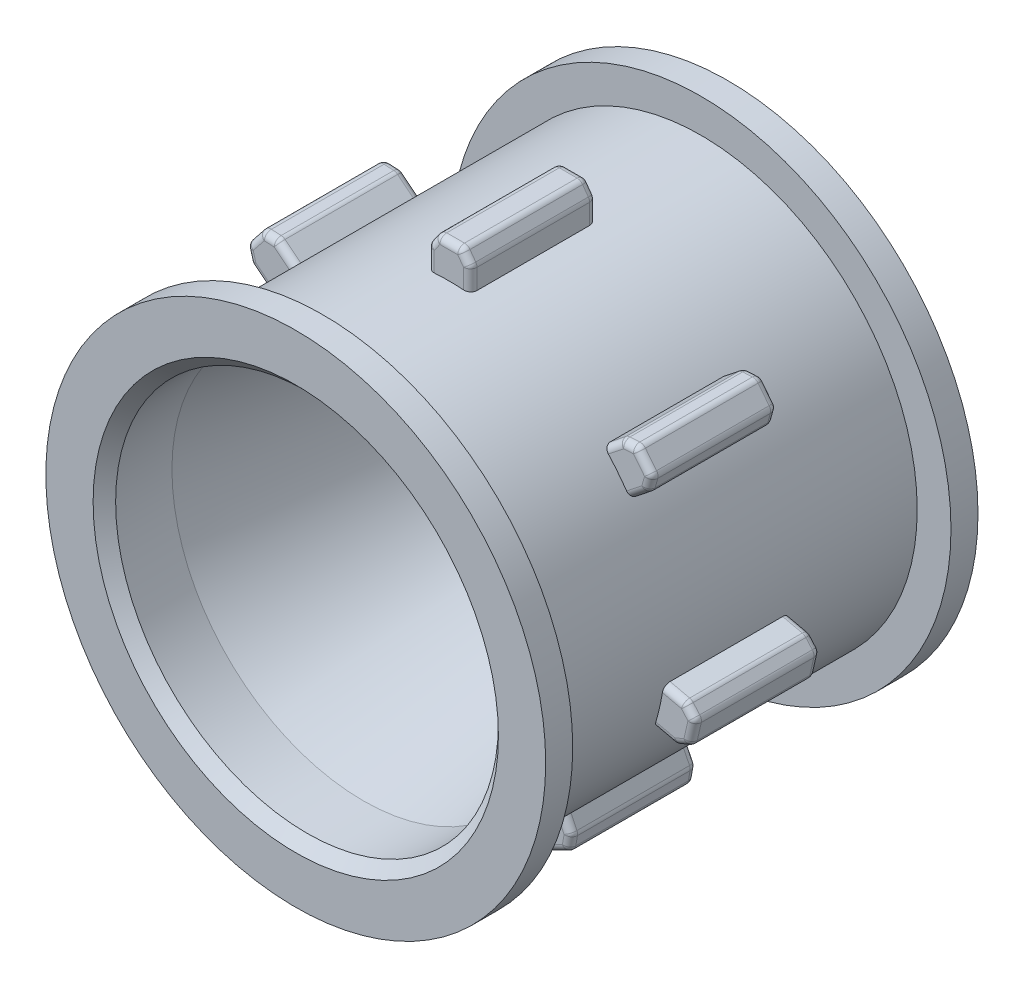
SolidWorks part; units mm, degrees
ref_plane "Ebene vorne" through (0, 0, 0) normal (0, 0, 1) x (1, 0, 0)
ref_plane "Ebene oben" through (0, 0, 0) normal (0, 1, 0) x (1, 0, 0)
ref_plane "Ebene rechts" through (0, 0, 0) normal (1, 0, 0) x (0, 0, -1)
sketch "Skizze1" plane through (0, 0, 0) normal (0, 0, 1) x (1, 0, 0)
  circle A0 centre (0, 0) radius 9.6
  dimension "D1" = 19.2
extrude "Laufrad" add sketch "Skizze1" along normal blind 8.4 and the other way blind 8.4
sketch "Skizze2" plane through (0, 0, 8.4) normal (0, 0, 1) x (1, 0, 0)
  circle A0 centre (0, 0) radius 11.1
  circle A1 centre (0, 0) radius 9.6 construction
  dimension "D1" = 1.5
extrude "Kettenführung" add sketch "Skizze2" along normal blind 1.2
mirror "Spiegeln Kettenführung" about plane through (0, 0, 0) normal (0, 0, 1) of "Kettenführung"
sketch "Skizze4" plane through (0, 0, -9.6) normal (0, 0, -1) x (-1, 0, 0)
  circle A0 centre (0, 0) radius 1
  dimension "D1" = 2
extrude "SchraubenBohrung M3" cut sketch "Skizze4" against normal through all
sketch "Skizze3" plane through (0, 0, -9.6) normal (0, 0, -1) x (-1, 0, 0)
  circle A0 centre (0, 0) radius 4.1
  dimension "D1" = 8.2
extrude "Kugellagersitz" cut sketch "Skizze3" against normal blind 2
sketch "Skizze5" plane through (0, 0, 0) normal (1, 0, 0) x (0, 0, -1)
  line L0 (-9.6, 0) -> (-9.6, 8.5)
  line L1 (-9.6, 8.5) -> (-6.6, 8.5)
  line L2 (-6.6, 8.5) -> (6.1, 6)
  line L3 (6.1, 6) -> (6.1, 0)
  line L4 (9.6, -4.1) -> (9.6, 4.1) construction
  line L5 (-9.6, 0) -> (7.6, 0) construction
  line L6 (-9.6, 0) -> (6.1, 0)
  line L7 (-9.6, 11.1) -> (-9.6, -11.1) construction
  dimension "D1" = 3.5
  dimension "D2" = 3
  dimension "D3" = 8.5
  dimension "D4" = 6
revolve "Schnitt-Rotation3" cut sketch "Skizze5" angle 360 about axis through (0, 0, -8.4) along (0, 0, 1)
chamfer "Fase1" distance 0.1 angle 45 1 edges at (-1, 0, -6.1) tangent propagation no
sketch "Skizze6" plane through (0, 0, 0) normal (0, 0, 1) x (1, 0, 0)
  line L0 (0, 0) -> (0, 10.3) construction
  line L1 (0, 10.3) -> (0, 11.1) construction
  line L2 (0.55, 11.1) -> (-0.55, 11.1)
  line L3 (-0.55, 11.1) -> (-0.95, 10.5424)
  line L4 (-0.95, 10.5424) -> (-0.95, 9.5529)
  line L5 (0.95, 10.5424) -> (0.95, 9.5529)
  line L6 (0.55, 11.1) -> (0.95, 10.5424)
  line L7 (-0.95, 9.5529) -> (0.95, 9.5529)
  circle A1 centre (0, 0) radius 9.6 construction
  dimension "D1" = 0.8
  dimension "D2" = 10.3
  dimension "D3" = 1.9
  dimension "D4" = 1.1
extrude "Zahn" add sketch "Skizze6" along normal blind 2.8 and the other way blind 2.8
fillet "Verrundung1" radius 0.3 14 edges at (0.95, 10.5424, 0) (-0.95, 10.5424, 0) (-0.95, 10.0476, -2.8) (-0.75, 10.8212, -2.8) (0, 11.1, -2.8) (0.75, 10.8212, -2.8) (0.95, 10.0476, -2.8) (-0.55, 11.1, 0) (0.55, 11.1, 0) (-0.95, 10.0476, 2.8) (-0.75, 10.8212, 2.8) (0, 11.1, 2.8) (0.75, 10.8212, 2.8) (0.95, 10.0476, 2.8)
pattern_circular "Kreismuster1" count 7 over 360 about axis through (0, 0, -8.4) along (0, 0, 1) of "Zahn", "Verrundung1"
sketch "Skizze8" plane through (0, 0, -9.6) normal (0, 0, -1) x (-1, 0, 0)
  line L0 (0, 11.1) -> (0, -11.1) construction
  line L1 (0, -11.1) -> (0, 11.1) construction
  line L2 (11.1, 0) -> (-11.1, 0) construction
  line L3 (2.1, 8.7) -> (2.1, -8.7)
  line L4 (2.1, -8.7) -> (-2.1, -8.7)
  line L5 (-2.1, -8.7) -> (-2.1, 8.7)
  line L6 (-2.1, 0) -> (2.1, 0)
  line L7 (2.1, 8.7) -> (-2.1, 8.7)
  circle A0 centre (0, 0) radius 11.1 construction
  point P12 (0, 0)
  dimension "D1" = 8.7
  dimension "D2" = 2.1
  dimension "D3" = 2.1
extrude "Auschnitt Antrieb Wage" cut sketch "Skizze8" against normal blind 2 contours L5 L6 L3 | L3 L7 L5 | L6 L5 L3 | L5 L4 L3 region at (0, 4.35, -9.6) region at (0, -4.35, -9.6)
sketch "Skizze10" plane through (0, 0, -9.6) normal (0, 0, -1) x (-1, 0, 0)
  line L0 (0, 11.1) -> (0, -11.1) construction
  line L1 (0, 10.56) -> (0, -10.56) construction
  line L2 (-8.5, 3.8) -> (8.5, 3.8)
  line L3 (8.5, 3.8) -> (8.5, -3.8)
  line L4 (8.5, -3.8) -> (-8.5, -3.8)
  line L5 (0, -3.8) -> (0, 3.8)
  line L6 (10.56, 0) -> (-10.56, 0) construction
  line L7 (-8.5, 3.8) -> (-8.5, -3.8)
  circle A0 centre (0, 0) radius 11.1 construction
  dimension "D1" = 8.5
  dimension "D2" = 3.8
  dimension "D3" = 3.8
extrude "Schnitt-Linear austragen2" cut sketch "Skizze10" against normal blind 2 contours L4 L3 L2 | L2 L7 L4 | L4 L5 L2 | L5 L4 L2 region at (4.25, 0, -9.6) region at (-4.25, 0, -9.6)
chamfer "Fase2" distance 0.5 angle 45 2 edges at (-6, 0, -6.1) (-8.5, 0, 9.6) first distance on face at (-1.1, 0, -6.1) first distance on face at (-8.5, 0, 9.6)
